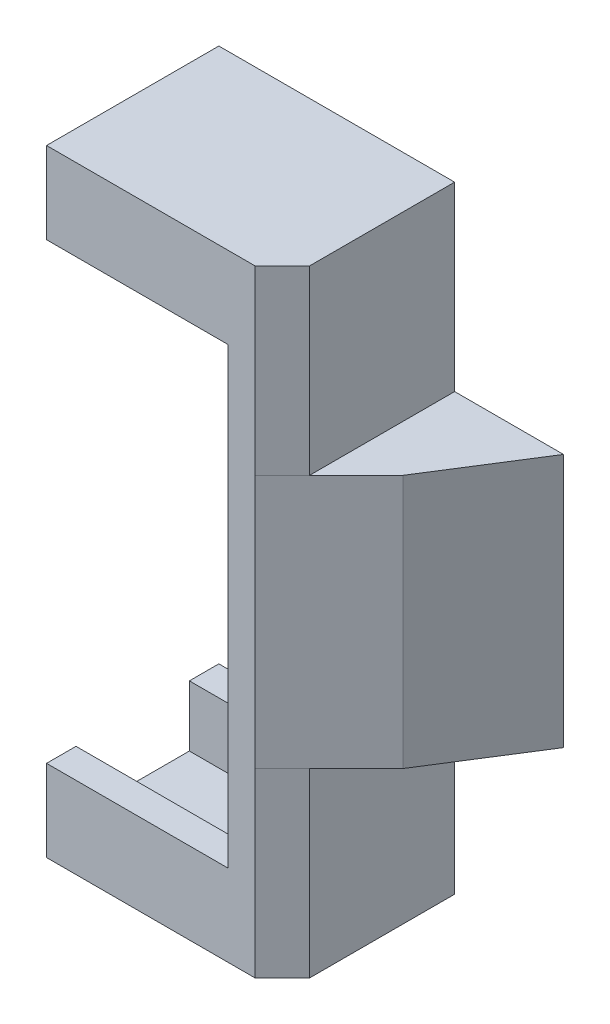
SolidWorks part; units mm, degrees
ref_plane "Front Plane" through (0, 0, 0) normal (0, 0, 1) x (1, 0, 0)
ref_plane "Top Plane" through (0, 0, 0) normal (0, 1, 0) x (1, 0, 0)
ref_plane "Right Plane" through (0, 0, 0) normal (1, 0, 0) x (0, 0, -1)
sketch "Sketch1" plane through (0, 0, 0) normal (0, 1, 0) x (1, 0, 0)
  line L0 (6.5, 4.75) -> (12.5, 4.75)
  line L1 (-6.5, 4.75) -> (6.5, 4.75)
  line L2 (-6.5, 4.75) -> (-6.5, -4.75)
  line L3 (-6.5, -4.75) -> (6.5, -4.75)
  line L5 (-6.5, 4.75) -> (6.5, -4.75) construction
  line L6 (-6.5, -4.75) -> (6.5, 4.75) construction
  line L7 (12.5, 4.75) -> (6.5, -4.75)
  point P0 (0, 0)
  dimension "D1" = 13
  dimension "D2" = 9.5
  dimension "D3" = 6
extrude "Boss-Extrude1" add sketch "Sketch1" along normal blind 34
sketch "Sketch2" plane through (-6.5, 0, 0) normal (-1, 0, 0) x (0, 0, 1)
  line L0 (-4.75, 34) -> (4.75, 0) construction
  line L2 (-3.125, 32.85) -> (3.125, 32.85)
  line L3 (-3.125, 32.85) -> (-3.125, 1.15)
  line L4 (-3.125, 1.15) -> (3.125, 1.15)
  line L5 (3.125, 32.85) -> (3.125, 1.15)
  line L6 (-3.125, 32.85) -> (3.125, 1.15) construction
  line L7 (-3.125, 1.15) -> (3.125, 32.85) construction
  point P4 (0, 17)
  dimension "D1" = 31.7
  dimension "D2" = 6.25
extrude "Cut-Extrude1" cut sketch "Sketch2" against normal blind 12
sketch "Sketch3" plane through (0, 0, 4.75) normal (0, 0, 1) x (1, 0, 0)
  line L0 (-6.5, 34) -> (6.5, 0) construction
  line L1 (3.5, 29.5) -> (-6.5, 29.5)
  line L2 (-6.5, 34) -> (-6.5, 0) construction
  line L3 (-6.5, 29.5) -> (-6.5, 4.5)
  line L4 (-6.5, 4.5) -> (3.5, 4.5)
  line L5 (-6.5, 0) -> (6.5, 34) construction
  line L6 (3.5, 4.5) -> (3.5, 29.5)
  point P14 (0, 17)
  dimension "D1" = 10
  dimension "D2" = 10
  dimension "D3" = 25
  dimension "D4" = 12.5
extrude "Cut-Extrude2" cut sketch "Sketch3" against normal blind 12
sketch "Sketch4" plane through (0, 0, 4.75) normal (0, 0, 1) x (1, 0, 0)
  line L0 (12.5, 34) -> (12.5, 0) construction
  line L1 (6.5, 34) -> (12.5, 34)
  line L2 (6.5, 34) -> (6.5, 24)
  line L3 (6.5, 24) -> (12.5, 24)
  line L4 (12.5, 34) -> (12.5, 24)
  line L6 (6.5, 0) -> (12.5, 0)
  line L7 (6.5, 0) -> (6.5, 10)
  line L8 (6.5, 10) -> (12.5, 10)
  line L9 (12.5, 0) -> (12.5, 10)
  dimension "D1" = 10
  dimension "D2" = 10
extrude "Cut-Extrude3" cut sketch "Sketch4" against normal blind 10
chamfer "Chamfer2" distance 1.5 angle 45 1 edges at (6.5, 29, 4.75)
chamfer "Chamfer3" distance 1.5 angle 45 1 edges at (6.5, 5, 4.75)
chamfer "Chamfer4" distance 1.5 angle 45 1 edges at (6.5, 17, 4.75) first distance on face at (1.1667, 17, 4.75)
